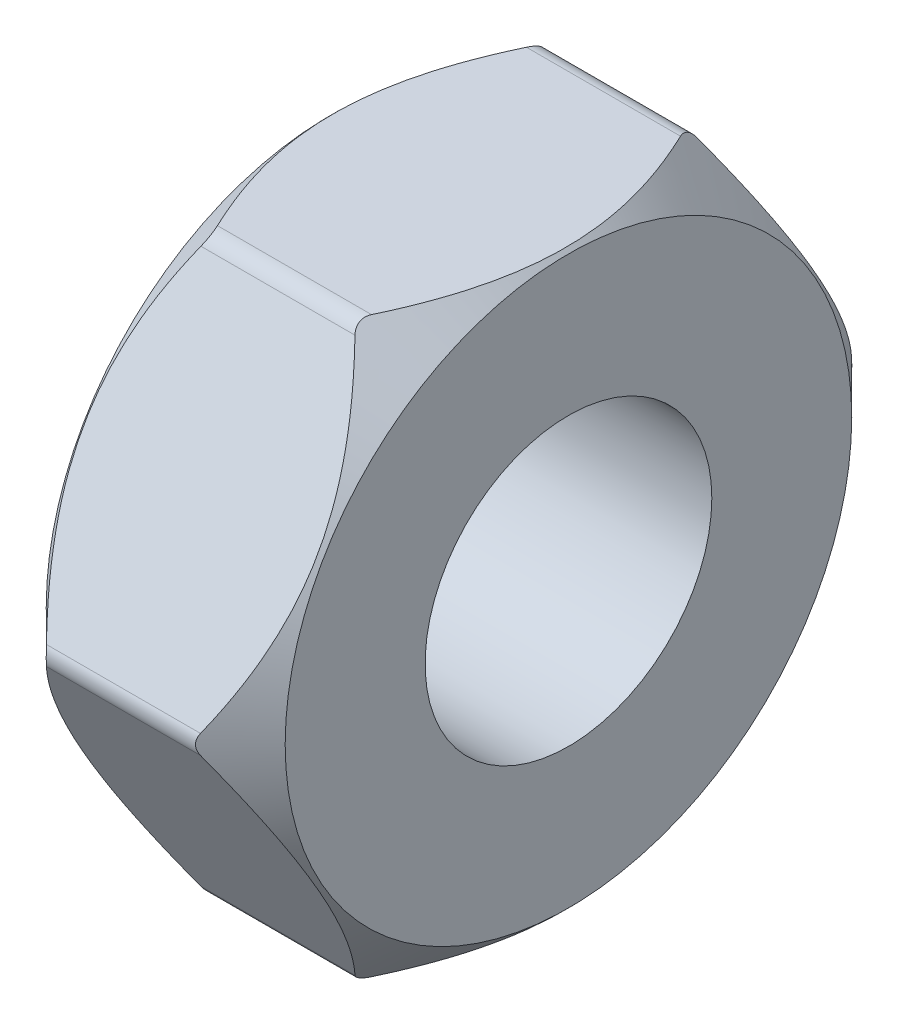
SolidWorks part; units mm, degrees
ref_plane "Plan de face" through (0, 0, 0) normal (0, 0, 1) x (1, 0, 0)
ref_plane "Plan de dessus" through (0, 0, 0) normal (0, 1, 0) x (1, 0, 0)
ref_plane "Plan de droite" through (0, 0, 0) normal (1, 0, 0) x (0, 0, -1)
sketch "Esquisse1" plane through (0, 0, 0) normal (1, 0, 0) x (0, 0, -1)
  line L1 (34.641, 0) -> (17.3205, 30)
  line L2 (17.3205, 30) -> (-17.3205, 30)
  line L3 (-17.3205, 30) -> (-34.641, 0)
  line L4 (-34.641, 0) -> (-17.3205, -30)
  line L5 (-17.3205, -30) -> (17.3205, -30)
  line L6 (17.3205, -30) -> (34.641, 0)
  circle A0 centre (0, 0) radius 30 construction
  circle A1 centre (0, 0) radius 15
  dimension "D3" = 30
  dimension "D1" = 60
  dimension "D2" = 60
extrude "Boss.-Extru.1" add sketch "Esquisse1" along normal blind 25
sketch "Esquisse2" plane through (0, 0, 0) normal (0, 1, 0) x (1, 0, 0)
  line L0 (0, -34.641) -> (0, -29.641)
  line L1 (0, -17.3205) -> (0, -34.641) construction
  line L2 (0, -29.641) -> (5, -34.641)
  line L3 (25, -34.641) -> (0, -34.641) construction
  line L4 (5, -34.641) -> (0, -34.641)
  line L5 (25, -34.641) -> (25, -29.641)
  line L6 (25, -17.3205) -> (25, -34.641) construction
  line L7 (25, -29.641) -> (20, -34.641)
  line L8 (20, -34.641) -> (25, -34.641)
  dimension "D1" = 5
  dimension "D2" = 5
  dimension "D3" = 5
  dimension "D4" = 5
sketch "Esquisse3" plane through (0, 0, 0) normal (0, 0, 1) x (1, 0, 0)
  line L0 (-5.5398, 0) -> (27.8519, 0) construction
revolve "Enlèvement de matière-Révolution2" cut sketch "Esquisse2" angle 360 about L0
fillet "Congé1" radius 2 6 edges at (12.5, 30, 17.3205) (12.5, 0, 34.641) (12.5, -30, 17.3205) (12.5, -30, -17.3205) (12.5, 0, -34.641) (12.5, 30, -17.3205)
chamfer "Chanfrein1" distance 2 angle 45 1 edges at (0, 0, -15)
sketch "Esquisse6" plane through (0, 0, 0) normal (-1, 0, 0) x (0, 0, 1)
  circle A0 centre (0, 0) radius 17
curve "Hélice/Spirale1" pitch 4 height 25 turns 6.25
ref_plane "Plan1" through (0, 0, 15) normal (0, 0, 1) x (1, 0, 0)
sketch "Esquisse15" plane through (0, 0, 15) normal (0, 0, 1) x (1, 0, 0)
  line L0 (-5.5398, 0) -> (27.8519, 0) construction
  line L1 (1.4997, 9) -> (2.9997, 11.5981)
  line L2 (2.9997, 11.5981) -> (-0.0003, 11.5981)
  line L3 (-0.0003, 11.5981) -> (1.4997, 9)
  circle A0 centre (1.4997, 10.7321) radius 0.866 construction
  dimension "D1" = 3
  dimension "D2" = 2.5981
  dimension "D3" = 9
sweep "Enlèvement de matière-Balayage3" cut profiles "Esquisse15" path "Hélice/Spirale1"
